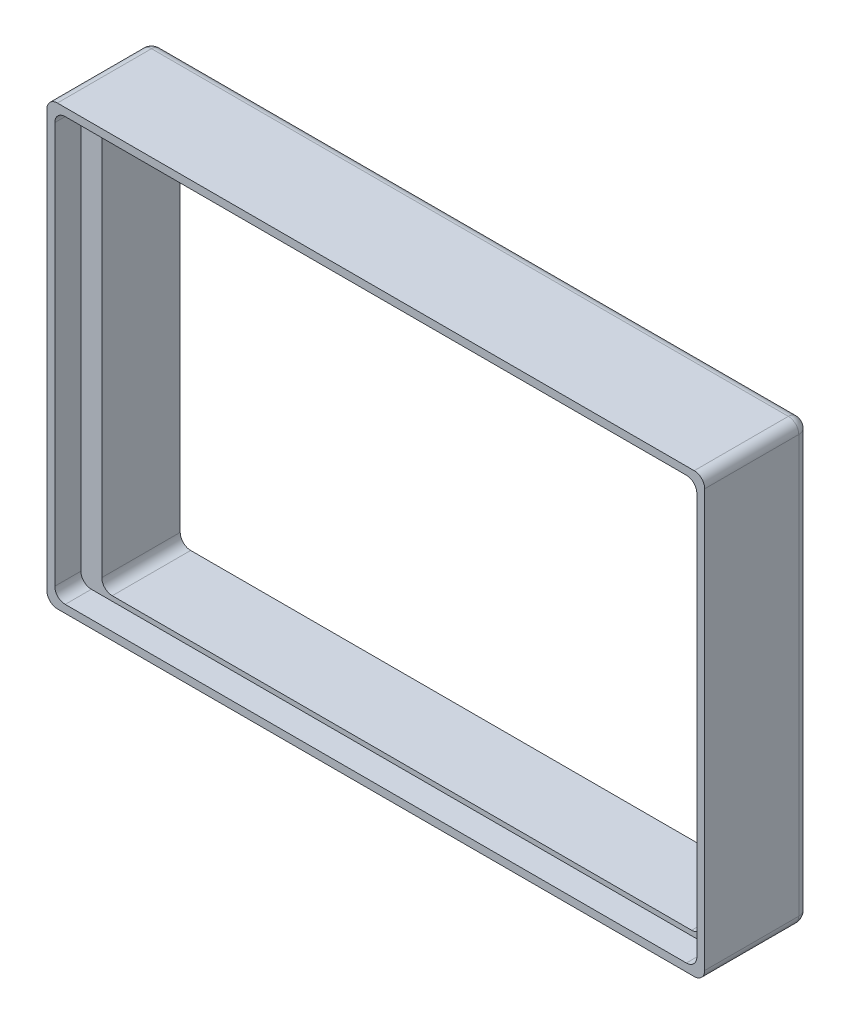
SolidWorks part; units mm, degrees
ref_plane "Front Plane" through (0, 0, 0) normal (0, 0, 1) x (1, 0, 0)
ref_plane "Top Plane" through (0, 0, 0) normal (0, 1, 0) x (1, 0, 0)
ref_plane "Right Plane" through (0, 0, 0) normal (1, 0, 0) x (0, 0, -1)
other "Configuration Table"
sketch "草图3" plane through (0, 0, 0) normal (0, 0, 1) x (1, 0, 0)
  line L1 (-62.905, 41.9) -> (62.905, 41.9)
  line L2 (-62.905, 41.9) -> (-62.905, -41.9)
  line L3 (-62.905, -41.9) -> (62.905, -41.9)
  line L4 (62.905, 41.9) -> (62.905, -41.9)
  line L5 (0, -41.9) -> (0, 41.9) construction
  line L6 (-62.905, 0) -> (62.905, 0) construction
  line L11 (0, -40.4) -> (0, 40.4) construction
  line L12 (-61.405, 0) -> (61.405, 0) construction
  point P0 (0, 0)
  point P4 (0, 0)
  dimension "D1" = 125.81
  dimension "D2" = 83.8
extrude "凸台-拉伸2" add sketch "草图3" along normal blind 20
sketch "草图5" plane through (0, 0, 20) normal (0, 0, 1) x (1, 0, 0)
  line L1 (-61.405, 40.4) -> (61.405, 40.4)
  line L2 (-61.405, 40.4) -> (-61.405, -40.4)
  line L3 (-61.405, -40.4) -> (61.405, -40.4)
  line L4 (61.405, 40.4) -> (61.405, -40.4)
  line L5 (0, -40.4) -> (0, 40.4) construction
  line L6 (-61.405, 0) -> (61.405, 0) construction
  point P0 (0, 0)
  dimension "D1" = 80.8
  dimension "D2" = 122.81
extrude "切除-拉伸1" cut sketch "草图5" against normal blind 5
sketch "草图6" plane through (0, 0, 0) normal (0, 0, -1) x (-1, 0, 0)
  line L1 (-57.41, 39.47) -> (57.41, 39.47)
  line L2 (-57.41, 39.47) -> (-57.41, -39.47)
  line L3 (-57.41, -39.47) -> (57.41, -39.47)
  line L4 (57.41, 39.47) -> (57.41, -39.47)
  line L5 (0, -39.47) -> (0, 39.47) construction
  line L6 (-57.41, 0) -> (57.41, 0) construction
  point P0 (0, 0)
  dimension "D1" = 78.94
  dimension "D2" = 114.82
extrude "切除-拉伸2" cut sketch "草图6" against normal blind 15
fillet "圆角1" radius 2 4 edges at (0, 41.9, 0) (-62.905, 0, 0) (0, -41.9, 0) (62.905, 0, 0)
fillet "圆角2" radius 2 8 edges at (-62.3192, 41.3142, 0.5858) (-62.3192, -41.3142, 0.5858) (62.3192, -41.3142, 0.5858) (62.905, 41.9, 11) (-62.905, 41.9, 11) (-62.905, -41.9, 11) (62.905, -41.9, 11) (62.3192, 41.3142, 0.5858)
fillet "圆角3" radius 2 8 edges at (-61.405, 40.4, 17.5) (-57.41, 39.47, 7.5) (57.41, 39.47, 7.5) (61.405, 40.4, 17.5) (61.405, -40.4, 17.5) (57.41, -39.47, 7.5) (-61.405, -40.4, 17.5) (-57.41, -39.47, 7.5)
